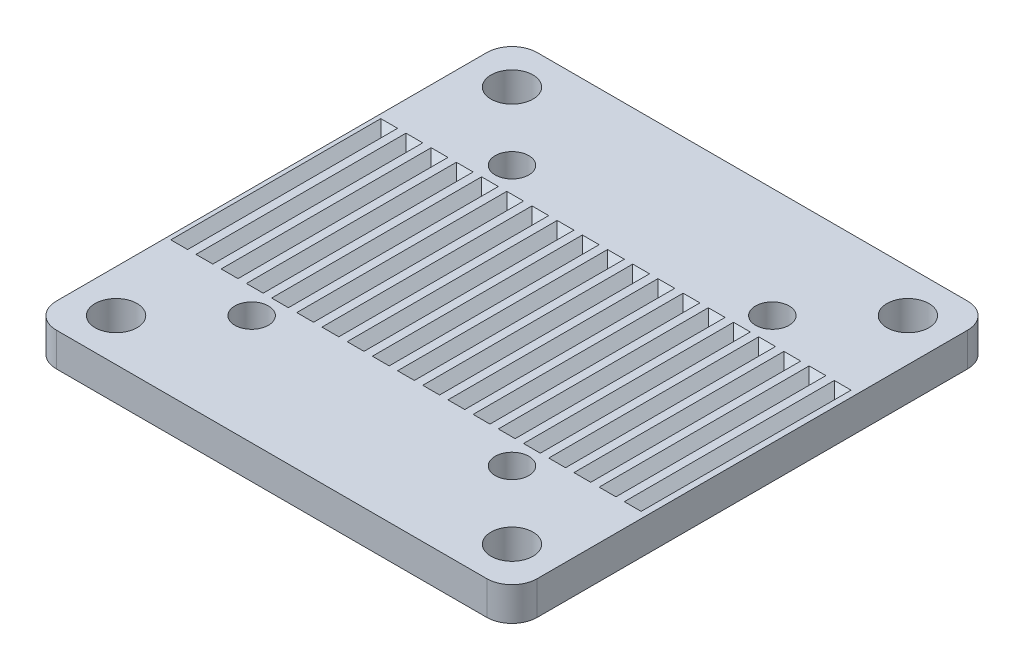
SolidWorks part; units mm, degrees
material "ABS"
ref_plane "Front Plane" through (0, 0, 0) normal (0, 0, 1) x (1, 0, 0)
ref_plane "Top Plane" through (0, 0, 0) normal (0, 1, 0) x (1, 0, 0)
ref_plane "Right Plane" through (0, 0, 0) normal (1, 0, 0) x (0, 0, -1)
sketch "Sketch1" plane through (0, 0, 0) normal (0, 1, 0) x (1, 0, 0)
  line L1 (25.625, 28.625) -> (-25.625, 28.625)
  line L2 (28.625, 25.625) -> (28.625, -25.625)
  line L3 (25.625, -28.625) -> (-25.625, -28.625)
  line L4 (-28.625, 25.625) -> (-28.625, -25.625)
  line L5 (28.625, 28.625) -> (-28.625, -28.625) construction
  line L6 (28.625, -28.625) -> (-28.625, 28.625) construction
  line L7 (23.57, -23.57) -> (-23.57, -23.57) construction
  line L8 (23.57, -23.57) -> (23.57, 23.57) construction
  line L9 (23.57, 23.57) -> (-23.57, 23.57) construction
  line L10 (-23.57, -23.57) -> (-23.57, 23.57) construction
  line L11 (23.57, -23.57) -> (-23.57, 23.57) construction
  line L12 (23.57, 23.57) -> (-23.57, -23.57) construction
  line L13 (15.5, 15.5) -> (-15.5, 15.5) construction
  line L14 (15.5, 15.5) -> (15.5, -15.5) construction
  line L15 (15.5, -15.5) -> (-15.5, -15.5) construction
  line L16 (-15.5, 15.5) -> (-15.5, -15.5) construction
  line L17 (15.5, 15.5) -> (-15.5, -15.5) construction
  line L18 (15.5, -15.5) -> (-15.5, 15.5) construction
  circle A0 centre (-15.5, 15.5) radius 2
  circle A1 centre (-23.57, 23.57) radius 2.5
  circle A2 centre (23.57, 23.57) radius 2.5
  circle A3 centre (15.5, 15.5) radius 2
  circle A4 centre (15.5, -15.5) radius 2
  circle A5 centre (-15.5, -15.5) radius 2
  circle A6 centre (-23.57, -23.57) radius 2.5
  circle A7 centre (23.57, -23.57) radius 2.5
  arc A8 (25.625, 28.625) -> (28.625, 25.625) centre (25.625, 25.625) cw
  arc A9 (28.625, -25.625) -> (25.625, -28.625) centre (25.625, -25.625) cw
  arc A10 (-25.625, -28.625) -> (-28.625, -25.625) centre (-25.625, -25.625) cw
  arc A11 (-25.625, 28.625) -> (-28.625, 25.625) centre (-25.625, 25.625) ccw
  point P0 (0, 0)
  point P5 (0, 0)
  point P11 (0, 0)
  dimension "D7" = 5
  dimension "D8" = 5
  dimension "D9" = 4
  dimension "D10" = 4
  dimension "D11" = 4
  dimension "D12" = 4
  dimension "D13" = 5
  dimension "D14" = 5
  dimension "D15" = 3
  dimension "D1" = 57.25
  dimension "D2" = 57.25
  dimension "D3" = 47.14
  dimension "D4" = 47.14
  dimension "D5" = 31
  dimension "D6" = 31
extrude "Boss-Extrude1" add sketch "Sketch1" along normal blind 4
ref_plane "Plane1" through (0, 0, 11.5) normal (0, 0, 1) x (1, 0, 0)
sketch "Sketch3" plane through (0, 0, 11.5) normal (0, 0, 1) x (1, 0, 0)
  line L0 (-28.125, 4) -> (-27.125, 3)
  line L1 (-25.625, 4) -> (-28.625, 4) construction
  line L2 (-27.125, 3) -> (-26.125, 4)
  line L3 (-26.125, 4) -> (-28.125, 4)
  line L4 (-27.125, 4) -> (-27.125, 3) construction
  line L5 (-28.625, 4) -> (-28.625, 0) construction
  line L6 (-25.125, 4) -> (-24.125, 3)
  line L7 (-23.125, 4) -> (-25.125, 4)
  line L8 (-24.125, 4) -> (-24.125, 3) construction
  line L9 (-24.125, 3) -> (-23.125, 4)
  line L10 (-22.125, 4) -> (-21.125, 3)
  line L11 (-20.125, 4) -> (-22.125, 4)
  line L12 (-21.125, 4) -> (-21.125, 3) construction
  line L13 (-21.125, 3) -> (-20.125, 4)
  line L14 (-19.125, 4) -> (-18.125, 3)
  line L15 (-17.125, 4) -> (-19.125, 4)
  line L16 (-18.125, 4) -> (-18.125, 3) construction
  line L17 (-18.125, 3) -> (-17.125, 4)
  line L18 (-16.125, 4) -> (-15.125, 3)
  line L19 (-14.125, 4) -> (-16.125, 4)
  line L20 (-15.125, 4) -> (-15.125, 3) construction
  line L21 (-15.125, 3) -> (-14.125, 4)
  line L22 (-13.125, 4) -> (-12.125, 3)
  line L23 (-11.125, 4) -> (-13.125, 4)
  line L24 (-12.125, 4) -> (-12.125, 3) construction
  line L25 (-12.125, 3) -> (-11.125, 4)
  line L26 (-10.125, 4) -> (-9.125, 3)
  line L27 (-8.125, 4) -> (-10.125, 4)
  line L28 (-9.125, 4) -> (-9.125, 3) construction
  line L29 (-9.125, 3) -> (-8.125, 4)
  line L30 (-7.125, 4) -> (-6.125, 3)
  line L31 (-5.125, 4) -> (-7.125, 4)
  line L32 (-6.125, 4) -> (-6.125, 3) construction
  line L33 (-6.125, 3) -> (-5.125, 4)
  line L34 (-4.125, 4) -> (-3.125, 3)
  line L35 (-2.125, 4) -> (-4.125, 4)
  line L36 (-3.125, 4) -> (-3.125, 3) construction
  line L37 (-3.125, 3) -> (-2.125, 4)
  line L38 (-1.125, 4) -> (-0.125, 3)
  line L39 (0.875, 4) -> (-1.125, 4)
  line L40 (-0.125, 4) -> (-0.125, 3) construction
  line L41 (-0.125, 3) -> (0.875, 4)
  line L42 (1.875, 4) -> (2.875, 3)
  line L43 (3.875, 4) -> (1.875, 4)
  line L44 (2.875, 4) -> (2.875, 3) construction
  line L45 (2.875, 3) -> (3.875, 4)
  line L46 (4.875, 4) -> (5.875, 3)
  line L47 (6.875, 4) -> (4.875, 4)
  line L48 (5.875, 4) -> (5.875, 3) construction
  line L49 (5.875, 3) -> (6.875, 4)
  line L50 (7.875, 4) -> (8.875, 3)
  line L51 (9.875, 4) -> (7.875, 4)
  line L52 (8.875, 4) -> (8.875, 3) construction
  line L53 (8.875, 3) -> (9.875, 4)
  line L54 (10.875, 4) -> (11.875, 3)
  line L55 (12.875, 4) -> (10.875, 4)
  line L56 (11.875, 4) -> (11.875, 3) construction
  line L57 (11.875, 3) -> (12.875, 4)
  line L58 (13.875, 4) -> (14.875, 3)
  line L59 (15.875, 4) -> (13.875, 4)
  line L60 (14.875, 4) -> (14.875, 3) construction
  line L61 (14.875, 3) -> (15.875, 4)
  line L62 (16.875, 4) -> (17.875, 3)
  line L63 (18.875, 4) -> (16.875, 4)
  line L64 (17.875, 4) -> (17.875, 3) construction
  line L65 (17.875, 3) -> (18.875, 4)
  line L66 (19.875, 4) -> (20.875, 3)
  line L67 (21.875, 4) -> (19.875, 4)
  line L68 (20.875, 4) -> (20.875, 3) construction
  line L69 (20.875, 3) -> (21.875, 4)
  line L70 (22.875, 4) -> (23.875, 3)
  line L71 (24.875, 4) -> (22.875, 4)
  line L72 (23.875, 4) -> (23.875, 3) construction
  line L73 (23.875, 3) -> (24.875, 4)
  line L74 (25.875, 4) -> (26.875, 3)
  line L75 (27.875, 4) -> (25.875, 4)
  line L76 (26.875, 4) -> (26.875, 3) construction
  line L77 (26.875, 3) -> (27.875, 4)
  dimension "D1" = 1
  dimension "D2" = 2
  dimension "D3" = 0.5
  dimension "D4" = 19
extrude "Cut-Extrude2" cut sketch "Sketch3" against normal blind 23
chamfer "Chamfer2" distance 1 angle 45 38 edges at (26.875, 4, -11.5) (23.875, 4, -11.5) (20.875, 4, -11.5) (17.875, 4, -11.5) (14.875, 4, -11.5) (11.875, 4, -11.5) (8.875, 4, -11.5) (5.875, 4, -11.5) (2.875, 4, -11.5) (-0.125, 4, -11.5) (-3.125, 4, -11.5) (-6.125, 4, -11.5) (-9.125, 4, -11.5) (-12.125, 4, -11.5) (-15.125, 4, -11.5) (-18.125, 4, -11.5) (-21.125, 4, -11.5) (-24.125, 4, -11.5) (-27.125, 4, -11.5) (26.875, 4, 11.5) (23.875, 4, 11.5) (20.875, 4, 11.5) (17.875, 4, 11.5) (14.875, 4, 11.5) (11.875, 4, 11.5) (8.875, 4, 11.5) (5.875, 4, 11.5) (2.875, 4, 11.5) (-0.125, 4, 11.5) (-3.125, 4, 11.5) (-6.125, 4, 11.5) (-9.125, 4, 11.5) (-12.125, 4, 11.5) (-15.125, 4, 11.5) (-18.125, 4, 11.5) (-21.125, 4, 11.5) (-24.125, 4, 11.5) (-27.125, 4, 11.5)
